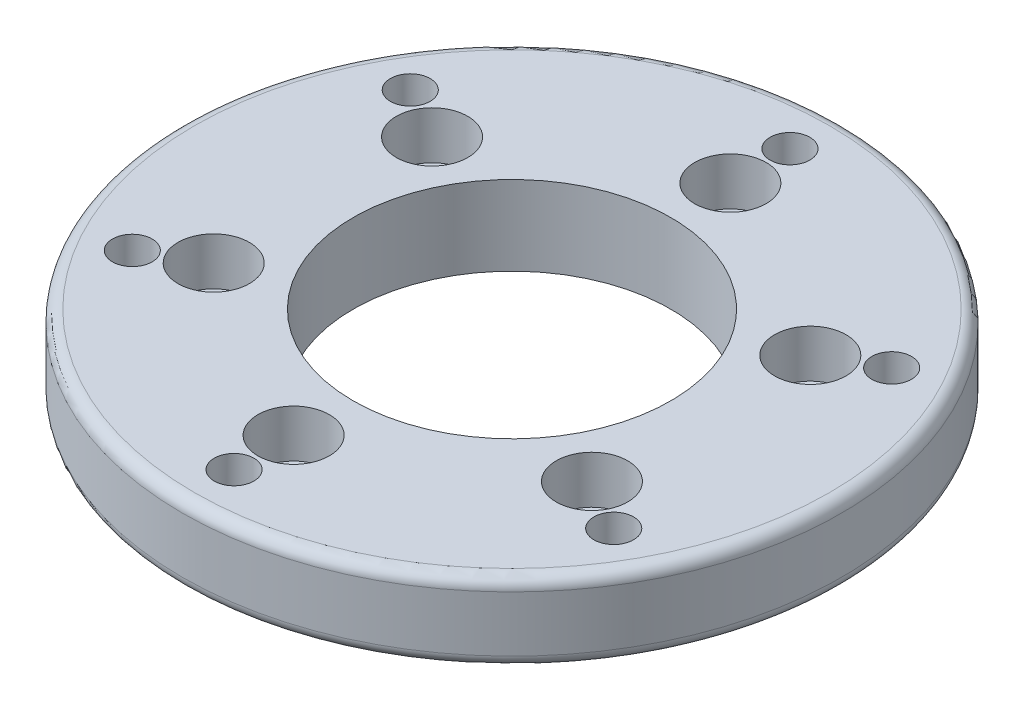
SolidWorks part; units mm, degrees
ref_plane "Ebene vorne" through (0, 0, 0) normal (0, 0, 1) x (1, 0, 0)
ref_plane "Ebene oben" through (0, 0, 0) normal (0, 1, 0) x (1, 0, 0)
ref_plane "Ebene rechts" through (0, 0, 0) normal (1, 0, 0) x (0, 0, -1)
sketch "Sketch1" plane through (0, 0, 0) normal (0, 1, 0) x (1, 0, 0)
  circle A0 centre (0, 0) radius 41.5
  dimension "D1" = 83
extrude "Main Plate" add sketch "Sketch1" along normal blind 10
sketch "Sketch2" plane through (0, 10, 0) normal (0, 1, 0) x (1, 0, 0)
  line L0 (0, 0) -> (0, 41.5) construction
  circle A1 centre (0, 0) radius 41.5 construction
  circle A2 centre (0, 27.5) radius 2.05
  circle A3 centre (23.8157, 13.75) radius 2.05
  circle A4 centre (23.8157, -13.75) radius 2.05
  circle A5 centre (0, -27.5) radius 2.05
  circle A6 centre (-23.8157, -13.75) radius 2.05
  circle A7 centre (-23.8157, 13.75) radius 2.05
  point P20 (0, 0)
  dimension "D1" = 27.5
  dimension "D2" = 4.1
extrude "G27" cut sketch "Sketch2" against normal through all
sketch "Sketch5" plane through (0, 10, 0) normal (0, 1, 0) x (1, 0, 0)
  circle A0 centre (0, 27.5) radius 4.5
  circle A1 centre (23.8157, 13.75) radius 4.5
  circle A2 centre (23.8157, -13.75) radius 4.5
  circle A3 centre (0, -27.5) radius 4.5
  circle A4 centre (-23.8157, -13.75) radius 4.5
  circle A5 centre (-23.8157, 13.75) radius 4.5
  point P15 (0, 0)
  dimension "D1" = 9
  dimension "D2" = 6
extrude "G27 Screw Heads" cut sketch "Sketch5" against normal blind 6
sketch "Sketch3" plane through (0, 10, 0) normal (0, 1, 0) x (1, 0, 0)
  line L0 (0, 0) -> (0, 41.5) construction
  circle A0 centre (0, 0) radius 41.5 construction
  circle A1 centre (0, 35) radius 2.5
  circle A3 centre (30.3109, 17.5) radius 2.5
  circle A4 centre (30.3109, -17.5) radius 2.5
  circle A5 centre (0, -35) radius 2.5
  circle A6 centre (-30.3109, -17.5) radius 2.5
  circle A7 centre (-30.3109, 17.5) radius 2.5
  point P22 (0, 0)
  dimension "D3" = 5
  dimension "D1" = 35
  dimension "D2" = 6
extrude "Momo - Sparko" cut sketch "Sketch3" against normal through all
sketch "Sketch6" plane through (0, 0, 0) normal (0, -1, 0) x (1, 0, 0)
  circle A0 centre (0, 35) radius 4.75
  circle A1 centre (30.3109, 17.5) radius 4.75
  circle A2 centre (30.3109, -17.5) radius 4.75
  circle A3 centre (0, -35) radius 4.75
  circle A4 centre (-30.3109, -17.5) radius 4.75
  circle A5 centre (-30.3109, 17.5) radius 4.75
  point P15 (0, 0)
  dimension "D1" = 9.5
  dimension "D2" = 6
extrude "Momo - Sparko Screw Heads" cut sketch "Sketch6" against normal blind 3
sketch "Sketch4" plane through (0, 10, 0) normal (0, 1, 0) x (1, 0, 0)
  circle A0 centre (0, 0) radius 20
  dimension "D1" = 40
extrude "Center Hole" cut sketch "Sketch4" against normal through all
fillet "Fillet1" radius 1.5 1 edges at (0, 10, 41.5) type face fillet first side face at (0, 10, 41.5) second side face at (0, 10, 20)
fillet "Fillet2" radius 1.5 1 edges at (0, 0, 41.5) type face fillet first side face at (0, 0, 20) second side face at (0, 8.5, 41.5)
